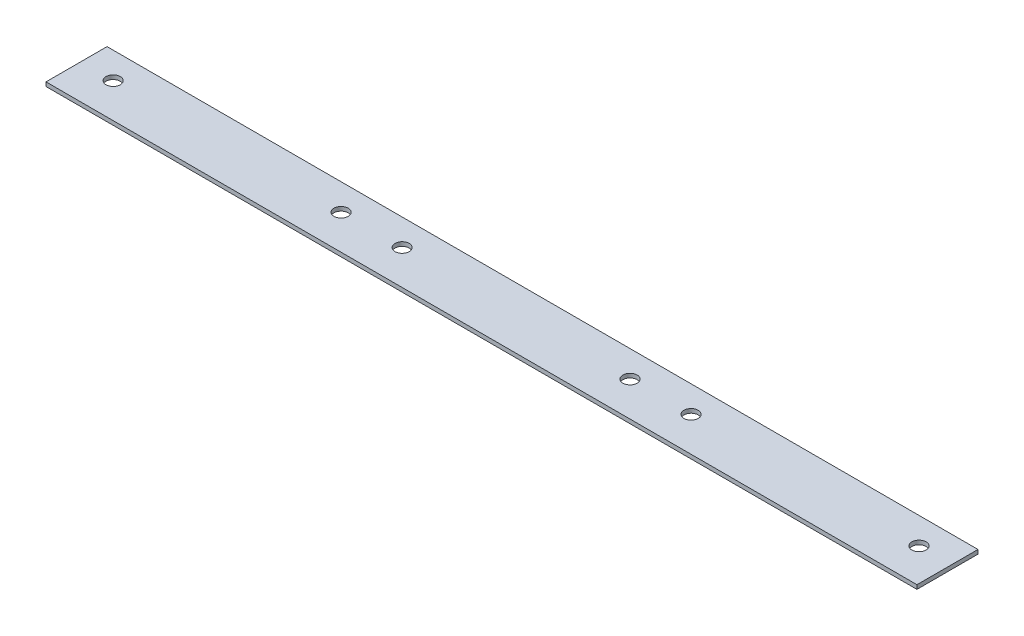
SolidWorks part; units mm, degrees
material "Простая углеродистая сталь"
ref_plane "Спереди" through (0, 0, 0) normal (0, 0, 1) x (1, 0, 0)
ref_plane "Сверху" through (0, 0, 0) normal (0, 1, 0) x (1, 0, 0)
ref_plane "Справа" through (0, 0, 0) normal (1, 0, 0) x (0, 0, -1)
sketch "Эскиз1" plane through (0, 0, 0) normal (0, 1, 0) x (1, 0, 0)
  line L1 (0, 0) -> (214, 0)
  line L2 (0, 0) -> (0, 15)
  line L3 (0, 15) -> (214, 15)
  line L4 (214, 0) -> (214, 15)
  circle A2 centre (64, 8.5) radius 1.75
  circle A3 centre (8, 8.5) radius 1.75
  circle A4 centre (79, 8.5) radius 1.75
  circle A5 centre (135, 8.5) radius 1.75
  circle A6 centre (150, 8.5) radius 1.75
  circle A7 centre (206, 8.5) radius 1.75
  dimension "D1" = 3
extrude "Бобышка-Вытянуть1" add sketch "Эскиз1" along normal blind 1
